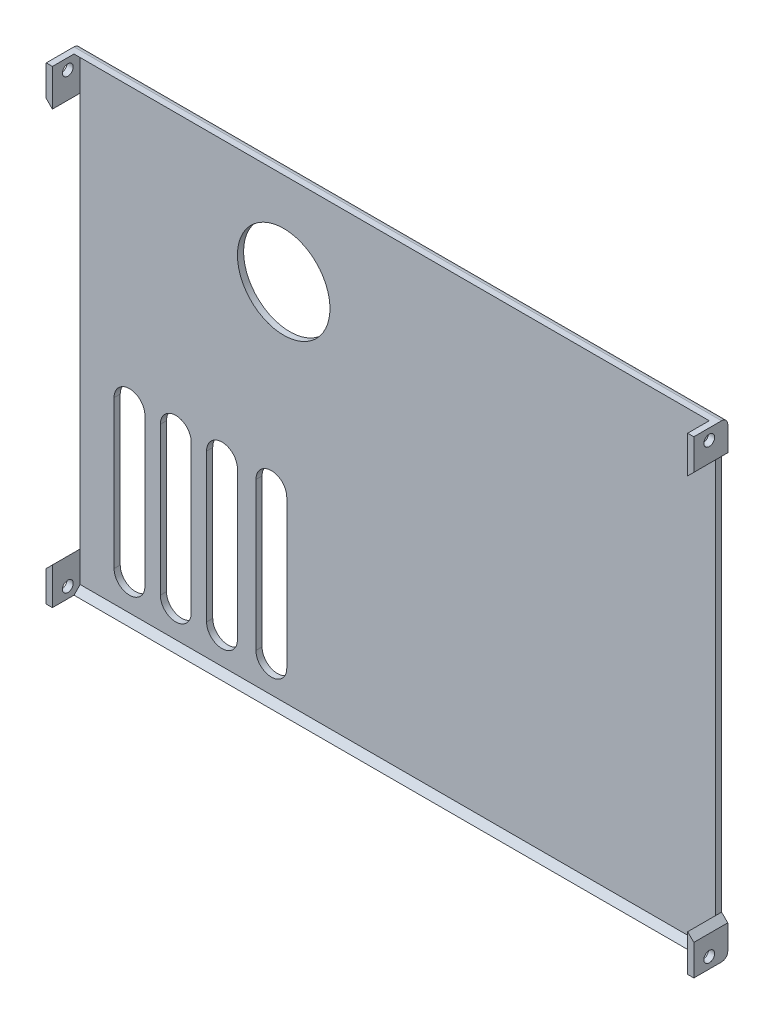
SolidWorks part; units mm, degrees
ref_plane "Front Plane" through (0, 0, 0) normal (0, 0, 1) x (1, 0, 0)
ref_plane "Top Plane" through (0, 0, 0) normal (0, 1, 0) x (1, 0, 0)
ref_plane "Right Plane" through (0, 0, 0) normal (1, 0, 0) x (0, 0, -1)
sketch "Sketch1" plane through (0, 0, 0) normal (0, 0, 1) x (1, 0, 0)
  line L1 (110, -90.3987) -> (-100, -90.3987)
  line L2 (110, -90.3987) -> (110, 61.6013)
  line L3 (110, 61.6013) -> (-100, 61.6013)
  line L4 (-100, -90.3987) -> (-100, 61.6013)
  line L5 (110, -90.3987) -> (-100, 61.6013) construction
  line L6 (110, 61.6013) -> (-100, -90.3987) construction
  point P0 (5, -14.3987)
  point P5 (0, 0)
  dimension "D1" = 210
  dimension "D2" = 152
extrude "body" add sketch "Sketch1" along normal blind 2
sketch "Sketch3" plane through (0, 0, 0) normal (0, 0, -1) x (-1, 0, 0)
  line L0 (100, -54.3987) -> (-110, -54.3987) construction
  line L1 (100, 61.6013) -> (100, -90.3987) construction
  line L2 (-110, -90.3987) -> (-110, 61.6013) construction
  line L3 (67, -78.3987) -> (67, -30.3987) construction
  line L4 (62, -78.3987) -> (62, -30.3987)
  line L5 (72, -78.3987) -> (72, -30.3987)
  line L6 (100, -30.3987) -> (-110, -30.3987) construction
  line L7 (82, -78.3987) -> (82, -30.3987) construction
  line L8 (100, -78.3987) -> (-110, -78.3987) construction
  line L9 (77, -78.3987) -> (77, -30.3987)
  line L10 (87, -78.3987) -> (87, -30.3987)
  line L11 (52, -78.3987) -> (52, -30.3987) construction
  line L12 (47, -78.3987) -> (47, -30.3987)
  line L13 (57, -78.3987) -> (57, -30.3987)
  line L14 (36, -78.3987) -> (36, -30.3987) construction
  line L15 (31, -78.3987) -> (31, -30.3987)
  line L16 (41, -78.3987) -> (41, -30.3987)
  line L17 (100, -90.3987) -> (100, 61.6013) construction
  line L18 (-110, 61.6013) -> (100, 61.6013) construction
  line L19 (100, -90.3987) -> (-110, -90.3987) construction
  line L20 (-110, -90.3987) -> (-110, 61.6013) construction
  circle A0 centre (32, 29.6013) radius 15
  arc A1 (62, -78.3987) -> (72, -78.3987) centre (67, -78.3987) ccw
  arc A2 (72, -30.3987) -> (62, -30.3987) centre (67, -30.3987) ccw
  arc A3 (77, -78.3987) -> (87, -78.3987) centre (82, -78.3987) ccw
  arc A4 (87, -30.3987) -> (77, -30.3987) centre (82, -30.3987) ccw
  arc A5 (47, -78.3987) -> (57, -78.3987) centre (52, -78.3987) ccw
  arc A6 (57, -30.3987) -> (47, -30.3987) centre (52, -30.3987) ccw
  arc A7 (31, -78.3987) -> (41, -78.3987) centre (36, -78.3987) ccw
  arc A8 (41, -30.3987) -> (31, -30.3987) centre (36, -30.3987) ccw
  point P10 (67, -54.3987)
  point P21 (82, -54.3987)
  point P27 (52, -54.3987)
  point P34 (36, -54.3987)
  dimension "D1" = 30
  dimension "D2" = 32
  dimension "D3" = 68
  dimension "D4" = 13
  dimension "D5" = 12
  dimension "D6" = 24
  dimension "D8" = 10
  dimension "D9" = 10
  dimension "D10" = 10
  dimension "D11" = 10
  dimension "D12" = 5
  dimension "D13" = 56
  dimension "D14" = 5
extrude "fan_exhaust_grill" cut sketch "Sketch3" against normal through all
fillet "Fillet1" radius 2 2 edges at (5, 61.6013, 0) (5, -90.3987, 0)
sketch "Sketch4" plane through (0, 0, 0) normal (0, 0, -1) x (-1, 0, 0)
  line L0 (100, -90.3987) -> (100, 61.6013) construction
  line L1 (100, -90.3987) -> (-110, -90.3987) construction
  line L3 (20, -18.3987) -> (95, -18.3987)
  line L4 (20, -18.3987) -> (20, -86.3987)
  line L5 (20, -86.3987) -> (95, -86.3987)
  line L6 (95, -18.3987) -> (95, -86.3987)
  line L7 (-59, 6.6013) -> (17, 6.6013)
  line L8 (-59, 6.6013) -> (-59, -86.3987)
  line L9 (-59, -86.3987) -> (17, -86.3987)
  line L10 (17, 6.6013) -> (17, -86.3987)
  circle A0 centre (32, 29.6013) radius 20
  dimension "D5" = 40
  dimension "D1" = 75
  dimension "D2" = 68
  dimension "D3" = 76
  dimension "D4" = 93
  dimension "D6" = 3
  dimension "D7" = 5
  dimension "D8" = 4
  dimension "D9" = 4
extrude "artwork" cut sketch "Sketch4" against normal blind 0.01
sketch "Sketch6" plane through (0, 0, 2) normal (0, 0, 1) x (1, 0, 0)
  line L0 (-100, 61.6013) -> (-100, -90.3987) construction
  line L1 (-100, 53.6013) -> (-98, 53.6013)
  line L2 (-100, 53.6013) -> (-100, -82.3987)
  line L3 (-100, -82.3987) -> (-98, -82.3987)
  line L4 (-98, 53.6013) -> (-98, -82.3987)
  line L5 (-100, 53.6013) -> (110, 53.6013) construction
  line L6 (110, -90.3987) -> (110, 61.6013) construction
  line L7 (-100, -82.3987) -> (110, -82.3987) construction
  line L9 (110, 61.6013) -> (-100, 61.6013) construction
  line L10 (110, 53.6013) -> (108, 53.6013)
  line L11 (110, 53.6013) -> (110, -82.3987)
  line L12 (110, -82.3987) -> (108, -82.3987)
  line L13 (108, 53.6013) -> (108, -82.3987)
  line L14 (-100, -90.3987) -> (110, -90.3987) construction
  dimension "D1" = 8
  dimension "D2" = 8
  dimension "D3" = 2
  dimension "D4" = 2
extrude "side_cut" cut sketch "Sketch6" against normal through all
sketch "Sketch7" plane through (0, 0, 2) normal (0, 0, 1) x (1, 0, 0)
  line L0 (-98, 53.6013) -> (-100, 53.6013) construction
  line L1 (-100, 61.6013) -> (-98, 61.6013)
  line L2 (-100, 61.6013) -> (-100, 53.6013)
  line L3 (-100, 53.6013) -> (-98, 53.6013)
  line L4 (-98, 61.6013) -> (-98, 53.6013)
  line L5 (-100, -82.3987) -> (-100, -90.3987) construction
  line L6 (-100, -82.3987) -> (-98, -82.3987)
  line L7 (-100, -82.3987) -> (-100, -90.3987)
  line L8 (-100, -90.3987) -> (-98, -90.3987)
  line L9 (-98, -82.3987) -> (-98, -90.3987)
  line L10 (-100, -90.3987) -> (110, -90.3987) construction
  line L11 (110, 61.6013) -> (-100, 61.6013) construction
  line L12 (110, 53.6013) -> (108, 53.6013)
  line L13 (110, 53.6013) -> (110, 61.6013)
  line L14 (110, 61.6013) -> (108, 61.6013)
  line L15 (108, 53.6013) -> (108, 61.6013)
  line L21 (110, -90.3987) -> (108, -90.3987)
  line L22 (110, -90.3987) -> (110, -82.3987)
  line L23 (110, -82.3987) -> (108, -82.3987)
  line L24 (108, -90.3987) -> (108, -82.3987)
  dimension "D1" = 2
  dimension "D2" = 2
  dimension "D3" = 2
  dimension "D6" = 8
extrude "mount_stubs" add sketch "Sketch7" along normal blind 9
sketch "Sketch8" plane through (110, 0, 0) normal (1, 0, 0) x (0, 0, -1)
  line L1 (0, -90.3987) -> (0, 61.6013) construction
  line L2 (0, 53.6013) -> (0, 59.6013) construction
  line L3 (-11, 61.6013) -> (-2, 61.6013) construction
  line L5 (-11, -90.3987) -> (-2, -90.3987) construction
  circle A0 centre (-6, 58.1013) radius 1.75
  circle A1 centre (-6, -86.8987) radius 1.75
  dimension "D1" = 3.5
  dimension "D5" = 3.5
  dimension "D2" = 6
  dimension "D3" = 3.5
  dimension "D4" = 3.5
  dimension "D6" = 6
extrude "mount_holes" cut sketch "Sketch8" against normal through all
fillet "Fillet4" radius 5 4 edges at (-95, -86.3987, 0.005) (-20, -86.3987, 0.005) (-95, -18.3987, 0.005) (-20, -18.3987, 0.005)
fillet "Fillet5" radius 2 4 edges at (59, -86.3987, 0.005) (-17, -86.3987, 0.005) (-17, 6.6013, 0.005) (59, 6.6013, 0.005)
sketch "Sketch9" plane through (0, 0, 2) normal (0, 0, 1) x (1, 0, 0)
  line L0 (-98, 53.6013) -> (-98, 61.6013) construction
  line L1 (108, 61.6013) -> (-98, 61.6013)
  line L2 (108, 61.6013) -> (108, 58.6013)
  line L3 (108, 58.6013) -> (-98, 58.6013)
  line L4 (-98, 61.6013) -> (-98, 58.6013)
  line L5 (-98, -90.3987) -> (-98, -82.3987) construction
  line L6 (108, -90.3987) -> (-98, -90.3987)
  line L7 (108, -90.3987) -> (108, -87.3987)
  line L8 (108, -87.3987) -> (-98, -87.3987)
  line L9 (-98, -90.3987) -> (-98, -87.3987)
  dimension "D1" = 3
  dimension "D2" = 3
extrude "Boss-Extrude2" add sketch "Sketch9" along normal blind 3
chamfer "Chamfer1" distance 4 angle 45 2 edges at (5, -87.3987, 5) (5, 58.6013, 5)
chamfer "Chamfer2" distance 4 angle 45 4 edges at (-98, 53.6013, 1) (-98, -82.3987, 1) (108, -82.3987, 1) (108, 53.6013, 1)
